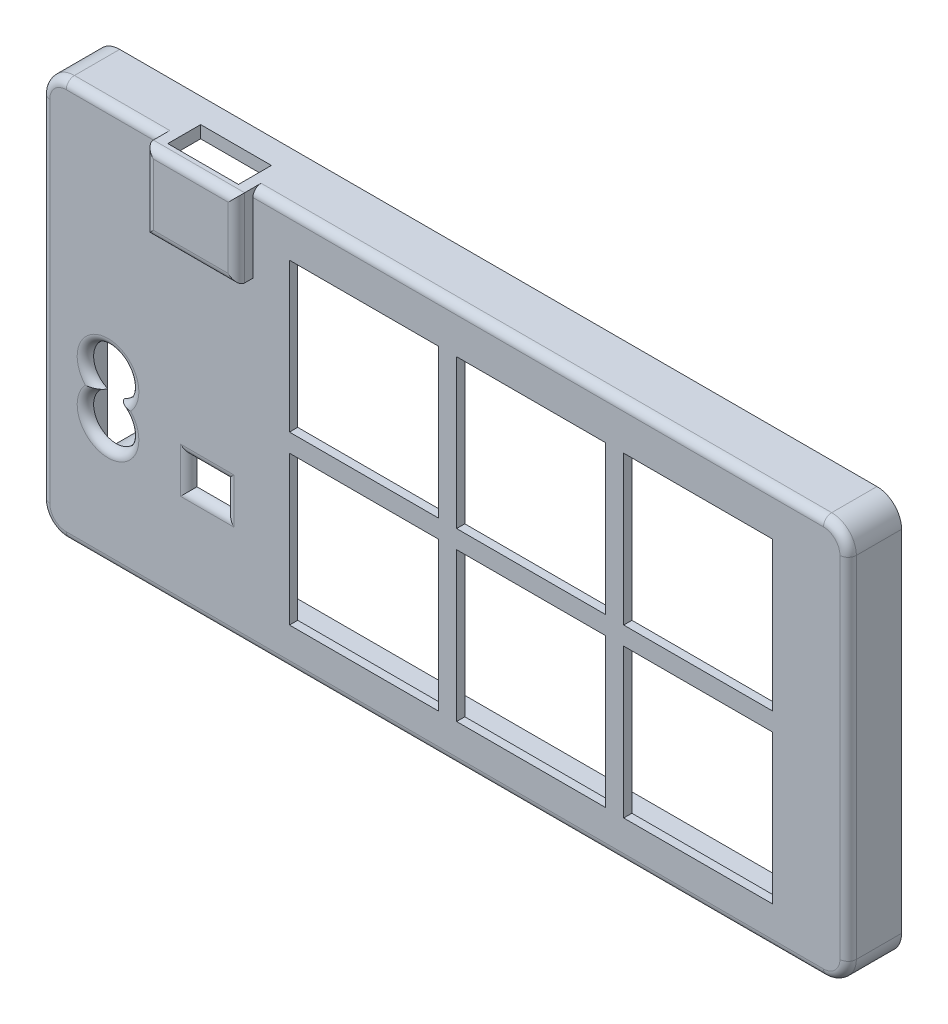
SolidWorks part; units mm, degrees
ref_plane "前视基准面" through (0, 0, 0) normal (0, 0, 1) x (1, 0, 0)
ref_plane "上视基准面" through (0, 0, 0) normal (0, 1, 0) x (1, 0, 0)
ref_plane "右视基准面" through (0, 0, 0) normal (1, 0, 0) x (0, 0, -1)
sketch "Sketch3" plane through (0, 0, 1.5) normal (0, 0, 1) x (1, 0, 0)
  line L4 (160.48, -134.445) -> (160.48, -85.9)
  line L5 (160.48, -85.9) -> (62.405, -85.9)
  line L6 (62.405, -85.9) -> (62.405, -134.445)
  line L7 (62.405, -134.445) -> (160.48, -134.445)
  line L8 (160.48, -134.445) -> (160.48, -85.9)
  line L9 (160.48, -85.9) -> (62.405, -85.9)
  line L10 (62.405, -85.9) -> (62.405, -134.445)
  line L11 (62.405, -134.445) -> (160.48, -134.445)
  line L12 (158.98, -87.4) -> (63.905, -87.4)
  line L13 (63.905, -87.4) -> (63.905, -132.945)
  line L14 (63.905, -132.945) -> (158.98, -132.945)
  line L15 (158.98, -132.945) -> (158.98, -87.4)
  line L16 (158.98, -87.4) -> (63.905, -87.4)
  line L17 (63.905, -87.4) -> (63.905, -132.945)
  line L18 (63.905, -132.945) -> (158.98, -132.945)
  line L19 (158.98, -132.945) -> (158.98, -87.4)
  dimension "D1" = 0
  dimension "D2" = 0
extrude "Wall" add sketch "Sketch3" along normal blind 6.5
sketch "Sketch4" plane through (0, 0, 8) normal (0, 0, 1) x (1, 0, 0)
  line L4 (62.405, -134.445) -> (160.48, -134.445)
  line L5 (160.48, -134.445) -> (160.48, -85.9)
  line L6 (160.48, -85.9) -> (62.405, -85.9)
  line L7 (62.405, -85.9) -> (62.405, -134.445)
  line L8 (62.405, -134.445) -> (160.48, -134.445)
  line L9 (160.48, -134.445) -> (160.48, -85.9)
  line L10 (160.48, -85.9) -> (62.405, -85.9)
  line L11 (62.405, -85.9) -> (62.405, -134.445)
  dimension "D1" = 0
extrude "TopFace" add sketch "Sketch4" against normal blind 1
sketch "Sketch7" plane through (0, 0, 7) normal (0, 0, -1) x (-1, 0, 0)
  circle A0 centre (-153.035, -93.345) radius 3
  circle A1 centre (-69.85, -93.98) radius 3
  circle A2 centre (-69.85, -127) radius 3
  circle A3 centre (-153.035, -127) radius 3
  dimension "D1" = 6
extrude "Standoffs" add sketch "Sketch7" along normal blind 5.5
hole_wizard "M2x0.4 Tapped Hole1" positions "Sketch10" profile "Sketch11" tap size "M2x0.4" standard "ANSI Metric"
sketch "Sketch10" plane through (0, 0, 1.5) normal (0, 0, -1) x (-1, 0, 0)
  point P0 (-153.035, -93.345)
  point P3 (-69.85, -93.98)
  point P6 (-153.035, -127)
  point P9 (-69.85, -127)
sketch "Sketch11" plane through (153.035, -93.345, 1.5) normal (1, 0, 0) x (0, 1, 0)
  line L0 (0, 0) -> (0, 4.4807)
  line L1 (0, 4.4807) -> (0.8, 4)
  line L2 (0.8, 4) -> (0.8, 0)
  line L5 (0.8, 0) -> (0, 0)
  line L10 (0, 4.4807) -> (-0.8, 4) construction
  line L11 (0, -6.35) -> (0, 107.95) construction
  dimension "Tap Drill Dia." = 1.6
  dimension "Tap Drill Depth" = 4
  dimension "Drill Angle" = 118
cosmetic thread "Hole Thread1" parameters "D1"=4, "D2"=2
cosmetic thread "Hole Thread2" parameters "D1"=4, "D2"=2
cosmetic thread "Hole Thread3" parameters "D1"=4, "D2"=2
cosmetic thread "Hole Thread4" parameters "D1"=4, "D2"=2
sketch "Sketch5" plane through (0, 0, 8) normal (0, 0, 1) x (1, 0, 0)
  line L1 (151.29, -129.7) -> (133.19, -129.7)
  line L2 (151.29, -129.7) -> (151.29, -111.6)
  line L3 (151.29, -111.6) -> (133.19, -111.6)
  line L4 (133.19, -129.7) -> (133.19, -111.6)
  line L5 (151.29, -129.7) -> (133.19, -111.6) construction
  line L6 (151.29, -111.6) -> (133.19, -129.7) construction
  line L7 (130.97, -129.7) -> (112.87, -129.7)
  line L8 (130.97, -129.7) -> (130.97, -111.6)
  line L9 (130.97, -111.6) -> (112.87, -111.6)
  line L10 (112.87, -129.7) -> (112.87, -111.6)
  line L11 (130.97, -129.7) -> (112.87, -111.6) construction
  line L12 (130.97, -111.6) -> (112.87, -129.7) construction
  line L13 (110.65, -129.7) -> (92.55, -129.7)
  line L14 (110.65, -129.7) -> (110.65, -111.6)
  line L15 (110.65, -111.6) -> (92.55, -111.6)
  line L16 (92.55, -129.7) -> (92.55, -111.6)
  line L17 (110.65, -129.7) -> (92.55, -111.6) construction
  line L18 (110.65, -111.6) -> (92.55, -129.7) construction
  line L19 (110.65, -109.38) -> (92.55, -109.38)
  line L20 (110.65, -109.38) -> (110.65, -91.28)
  line L21 (110.65, -91.28) -> (92.55, -91.28)
  line L22 (92.55, -109.38) -> (92.55, -91.28)
  line L23 (110.65, -109.38) -> (92.55, -91.28) construction
  line L24 (110.65, -91.28) -> (92.55, -109.38) construction
  line L25 (151.29, -109.38) -> (133.19, -109.38)
  line L26 (151.29, -109.38) -> (151.29, -91.28)
  line L27 (151.29, -91.28) -> (133.19, -91.28)
  line L28 (133.19, -109.38) -> (133.19, -91.28)
  line L29 (151.29, -109.38) -> (133.19, -91.28) construction
  line L30 (151.29, -91.28) -> (133.19, -109.38) construction
  line L31 (112.87, -91.28) -> (130.97, -91.28)
  line L32 (112.87, -91.28) -> (112.87, -109.38)
  line L33 (112.87, -109.38) -> (130.97, -109.38)
  line L34 (130.97, -91.28) -> (130.97, -109.38)
  line L35 (112.87, -91.28) -> (130.97, -109.38) construction
  line L36 (112.87, -109.38) -> (130.97, -91.28) construction
  line L37 (84.8, -121.77) -> (80.3, -121.77)
  line L38 (84.8, -121.77) -> (84.8, -118.27)
  line L39 (84.8, -118.27) -> (80.3, -118.27)
  line L40 (80.3, -121.77) -> (80.3, -118.27)
  line L41 (82.55, -121.77) -> (82.55, -118.27) construction
  line L43 (84.8, -120.02) -> (80.3, -120.02) construction
  arc A0 (71.539, -116.84) -> (69.431, -116.84) centre (70.485, -114.3) ccw
  arc A1 (69.431, -116.84) -> (71.539, -116.84) centre (70.485, -119.38) ccw
  circle A2 centre (90.17, -90.17) radius 0.55 construction
  circle A3 centre (74.93, -123.19) radius 0.55 construction
  point P0 (142.24, -120.65)
  point P6 (121.92, -120.65)
  point P12 (101.6, -120.65)
  point P18 (101.6, -100.33)
  point P24 (142.24, -100.33)
  point P30 (121.92, -100.33)
  dimension "D9" = 5.5
  dimension "D10" = 4.5
  dimension "D13" = 29.85
  dimension "D1" = 18.1
  dimension "D2" = 18.1
  dimension "D3" = 18.1
  dimension "D4" = 18.1
  dimension "D5" = 18.1
  dimension "D6" = 18.1
  dimension "D7" = 18.1
  dimension "D8" = 18.1
  dimension "D11" = 3.5
  dimension "D12" = 7.62
extrude "KeyCut" cut sketch "Sketch5" against normal through all
sketch "Sketch9" plane through (0, 0, 8) normal (0, 0, 1) x (1, 0, 0)
  line L0 (157.48, -85.9) -> (65.405, -85.9) construction
  line L1 (88.1, -95.4) -> (77, -95.4)
  line L2 (88.1, -95.4) -> (88.1, -85.9)
  line L3 (88.1, -85.9) -> (77, -85.9)
  line L4 (77, -95.4) -> (77, -85.9)
  line L5 (82.55, -95.4) -> (82.55, -85.9) construction
  circle A0 centre (74.93, -90.17) radius 0.55 construction
  circle A1 centre (90.17, -90.17) radius 0.55 construction
  dimension "D1" = 11.1
  dimension "D2" = 0
  dimension "D3" = 5.23
  dimension "D4" = 7.62
extrude "USBExtrude" add sketch "Sketch9" along normal blind 2
sketch "Sketch12" plane through (0, -85.9, 0) normal (0, 1, 0) x (1, 0, 0)
  line L0 (88.1, -10) -> (77, -10) construction
  line L1 (86.85, -8.5) -> (78.25, -8.5)
  line L2 (86.85, -8.5) -> (86.85, -4.5)
  line L3 (86.85, -4.5) -> (78.25, -4.5)
  line L4 (78.25, -8.5) -> (78.25, -4.5)
  line L5 (77, -8) -> (62.405, -8) construction
  point P6 (82.55, -10)
  point P7 (82.55, -8.5)
  dimension "D1" = 4
  dimension "D2" = 8.6
  dimension "D3" = 0.5
extrude "USBCut" cut sketch "Sketch12" against normal blind 8
fillet "FilletSide" radius 3 4 edges at (160.48, -134.445, 4.75) (62.405, -134.445, 4.75) (62.405, -85.9, 4.75) (160.48, -85.9, 4.75)
fillet "FilletSideInner" radius 1.5 4 edges at (63.905, -87.4, 4.25) (158.98, -87.4, 4.25) (158.98, -132.945, 4.25) (63.905, -132.945, 4.25)
fillet "FilletTop" radius 1 19 edges at (82.55, -95.4, 10) (77, -90.65, 10) (82.55, -85.9, 10) (88.1, -90.65, 10) (71.2025, -85.9, 8) (63.2837, -86.7787, 8) (62.405, -110.1725, 8) (63.2837, -133.5663, 8) (111.4425, -134.445, 8) (159.6013, -133.5663, 8) (160.48, -110.1725, 8) (159.6013, -86.7787, 8) (122.79, -85.9, 8) (82.55, -121.77, 8) (84.8, -120.02, 8) (82.55, -118.27, 8) (80.3, -120.02, 8) (70.485, -122.13, 8) (70.485, -111.55, 8)
fillet "FilletTopInner" radius 1 4 edges at (156.0214, -93.0592, 7) (156.035, -127, 7) (72.85, -93.98, 7) (72.85, -127, 7)
